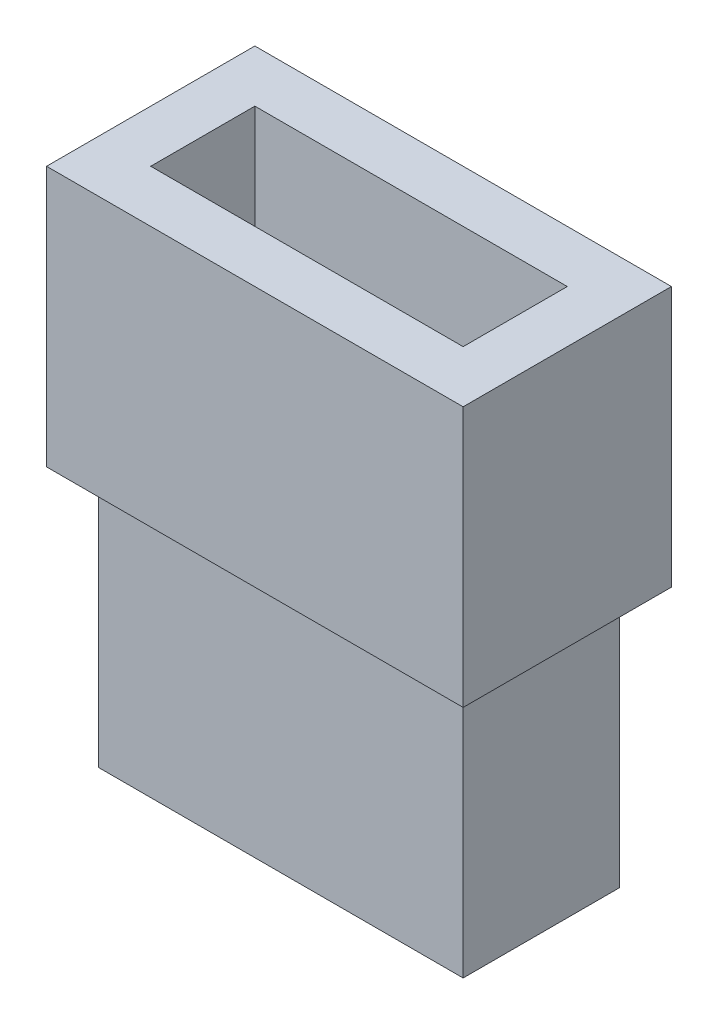
SolidWorks part; units mm, degrees
material "Delrin 2700 NC010, Low Viscosity Acetal Copolymer (SS)"
ref_plane "Front" through (0, 0, 0) normal (0, 0, 1) x (1, 0, 0)
ref_plane "Top" through (0, 0, 0) normal (0, 1, 0) x (1, 0, 0)
ref_plane "Right" through (0, 0, 0) normal (1, 0, 0) x (0, 0, -1)
sketch "Sketch1" plane through (0, 0, 0) normal (0, 1, 0) x (1, 0, 0)
  line L0 (17.5, -7.5) -> (17.5, 7.5)
  line L1 (-20, -10) -> (20, -10)
  line L2 (-20, -10) -> (-20, 10)
  line L3 (-20, 10) -> (20, 10)
  line L4 (20, -10) -> (20, 10)
  line L5 (-20, -10) -> (20, 10) construction
  line L6 (-20, 10) -> (20, -10) construction
  line L7 (-15, -5) -> (15, -5)
  line L8 (-15, -5) -> (-15, 5)
  line L9 (-15, 5) -> (15, 5)
  line L10 (15, -5) -> (15, 5)
  line L11 (-15, -5) -> (15, 5) construction
  line L12 (-15, 5) -> (15, -5) construction
  line L13 (-17.5, 7.5) -> (17.5, 7.5)
  line L14 (-17.5, -7.5) -> (-17.5, 7.5)
  line L15 (-17.5, -7.5) -> (17.5, -7.5)
  point P0 (0, 0)
  point P6 (0, 0)
  point P15 (15, 5.456)
  dimension "D1" = 40
  dimension "D2" = 5
  dimension "D3" = 2.5
  dimension "D4" = 20
  dimension "D5" = 2.5
extrude "Boss-Extrude1" add sketch "Sketch1" along normal blind 25 contours L14 L15 L0 L13 L10 L7 L8 L9 | L1 L4 L3 L2 L15 L14 L13 L0 region at (0, 0, 7.1192) region at (-19.5528, 0, 0)
extrude "Boss-Extrude2" add sketch "Sketch1<3>" against normal blind 25 contours L14 L15 L0 L13 L10 L7 L8 L9 region at (0, 0, 7.1192)
sketch "Sketch1<3>" plane through (0, 0, 0) normal (0, 1, 0) x (1, 0, 0) same geometry as "Sketch1"
